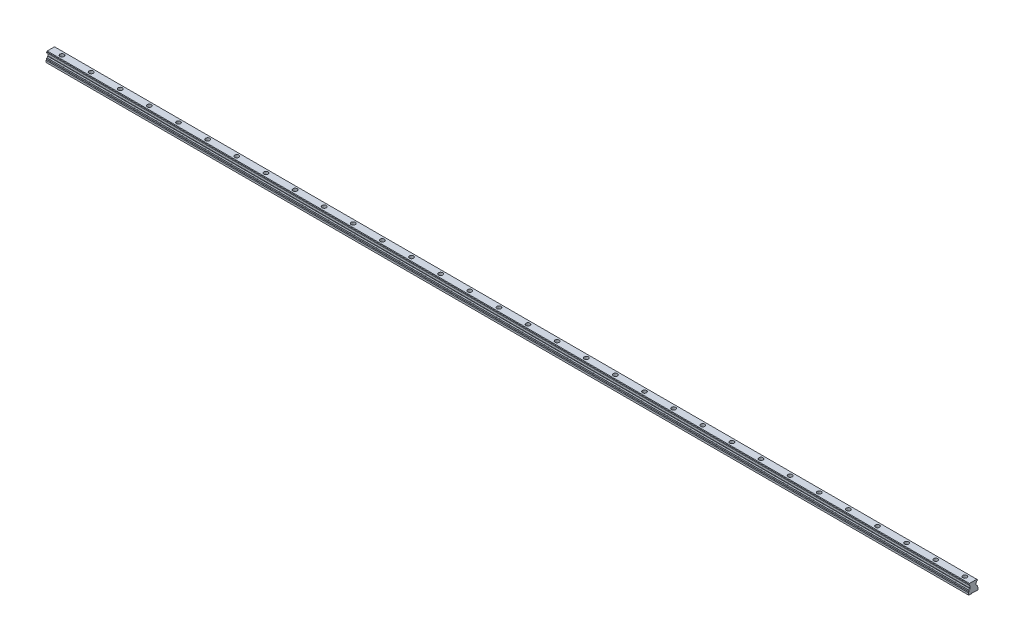
SolidWorks part; units mm, degrees
ref_plane "Front Plane" through (0, 0, 0) normal (0, 0, 1) x (1, 0, 0)
ref_plane "Top Plane" through (0, 0, 0) normal (0, 1, 0) x (1, 0, 0)
ref_plane "Right Plane" through (0, 0, 0) normal (1, 0, 0) x (0, 0, -1)
ref_plane "Plane1" through (58.5, 0, 0) normal (1, 0, 0) x (0, 0, -1)
sketch "Sketch7" plane through (58.5, 0, 0) normal (1, 0, 0) x (0, 0, -1)
  line L30 (-7.709, 8.8831) -> (-8.5, 8.6011)
  line L32 (-8.75, 5.6717) -> (-10, 4.95)
  line L35 (-10, 4.95) -> (-10, 1)
  line L37 (-10, 1) -> (-9, 0)
  line L39 (-4, 0) -> (-3.5, 0.5)
  line L42 (-3.5, 0.5) -> (3.5, 0.5)
  line L48 (3.5, 0.5) -> (4, 0)
  line L52 (4, 0) -> (9, 0)
  line L57 (-8.5, 8.6011) -> (-8.5, 6.1047)
  line L61 (-9, 0) -> (-4, 0)
  line L69 (8.5, 6.1047) -> (8.5, 8.4669)
  line L71 (6.5033, 10.3667) -> (6, 10.87)
  line L72 (6, 10.87) -> (6, 14.93)
  line L73 (6, 14.93) -> (6.5033, 15.4333)
  line L75 (8.5, 17.1989) -> (8.5, 19.3)
  line L77 (7.5, 20.3) -> (-7.5, 20.3)
  line L79 (-8.5, 19.3) -> (-8.5, 17.3331)
  line L81 (-6.5033, 15.4333) -> (-6, 14.93)
  line L82 (-6, 14.93) -> (-6, 10.87)
  line L83 (-6, 10.87) -> (-6.5033, 10.3667)
  line L85 (9, 0) -> (10, 1)
  line L87 (10, 1) -> (10, 4.95)
  line L89 (10, 4.95) -> (8.75, 5.6717)
  line L91 (8.5, 8.4669) -> (8.0847, 8.8822)
  line L93 (7.709, 16.9169) -> (8.5, 17.1989)
  line L95 (8.5, 19.3) -> (7.5, 20.3)
  line L97 (-7.5, 20.3) -> (-8.5, 19.3)
  line L99 (-8.5, 17.3331) -> (-8.0847, 16.9178)
  arc A8 (-8.75, 5.6717) -> (-8.5, 6.1047) centre (-9, 6.1047) ccw
  arc A12 (-7.709, 8.8831) -> (-6.5033, 10.3667) centre (-7.9, 10.27) ccw
  arc A15 (6.5033, 10.3667) -> (8.0847, 8.8822) centre (7.9, 10.27) ccw
  arc A16 (7.709, 16.9169) -> (6.5033, 15.4333) centre (7.9, 15.53) ccw
  arc A17 (-6.5033, 15.4333) -> (-8.0847, 16.9178) centre (-7.9, 15.53) ccw
  arc A19 (8.5, 6.1047) -> (8.75, 5.6717) centre (9, 6.1047) ccw
sketch "Sketch1" [suppressed] plane through (58.5, 0, 0) normal (1, 0, 0) x (0, 0, -1)
  line L0 (-8.5, 0) -> (8.5, 0)
  line L1 (8.5, 0) -> (8.5, 9.0051)
  line L2 (6.5033, 10.3667) -> (6, 10.87)
  line L3 (6, 10.87) -> (6, 14.93)
  line L4 (6, 14.93) -> (6.5033, 15.4333)
  line L5 (8.5, 16.7949) -> (8.5, 20.3)
  line L6 (8.5, 20.3) -> (-8.5, 20.3)
  line L7 (-8.5, 20.3) -> (-8.5, 16.7949)
  line L8 (-6.5033, 15.4333) -> (-6, 14.93)
  line L9 (-6, 14.93) -> (-6, 10.87)
  line L10 (-6, 10.87) -> (-6.5033, 10.3667)
  line L11 (-8.5, 9.0051) -> (-8.5, 0)
  arc A0 (8.5, 9.0051) -> (6.5033, 10.3667) centre (7.9, 10.27) cw
  arc A1 (6.5033, 15.4333) -> (8.5, 16.7949) centre (7.9, 15.53) cw
  arc A2 (-8.5, 16.7949) -> (-6.5033, 15.4333) centre (-7.9, 15.53) cw
  arc A3 (-6.5033, 10.3667) -> (-8.5, 9.0051) centre (-7.9, 10.27) cw
extrude "Boss-Extrude5" add sketch "Sketch7" along normal blind 1900
sketch "Sketch8" plane through (0, 20.3, 0) normal (0, 1, 0) x (1, 0, 0)
  line L0 (2009.9793, 0) -> (1889.6882, 0) construction
  circle A0 centre (1941.4917, 0) radius 4.25
  point P5 (1941.4917, 0)
  dimension "D1" = 8.5
extrude "Cut-Extrude1" cut sketch "Sketch8" against normal blind 9
sketch "Sketch9" plane through (0, 11.3, 0) normal (0, 1, 0) x (1, 0, 0)
  circle A0 centre (1941.4917, 0) radius 3
  dimension "D1" = 6
extrude "Cut-Extrude2" cut sketch "Sketch9" against normal through all
pattern_linear "LPattern1" count 35 spacing 60 along (-1, 0, 0) of "Cut-Extrude1", "Cut-Extrude2"
